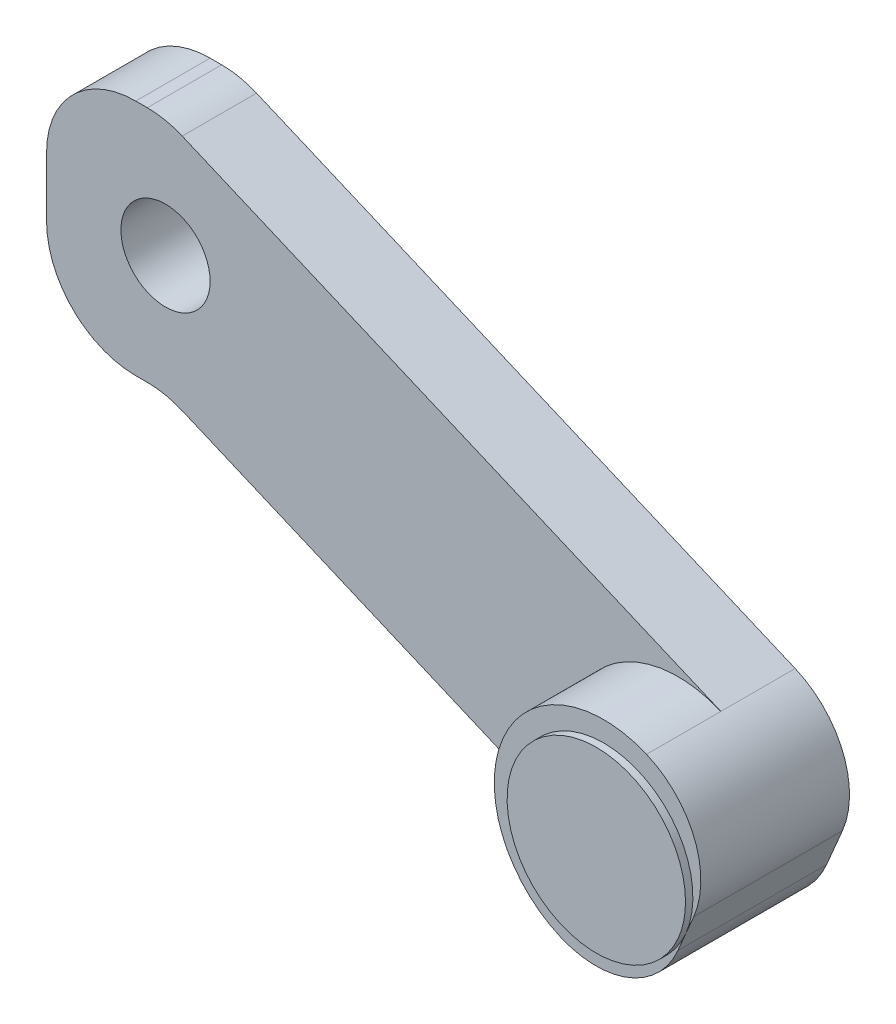
SolidWorks part; units mm, degrees
ref_plane "Plano frontal" through (0, 0, 0) normal (0, 0, 1) x (1, 0, 0)
ref_plane "Plano superior" through (0, 0, 0) normal (0, 1, 0) x (1, 0, 0)
ref_plane "Plano direito" through (0, 0, 0) normal (1, 0, 0) x (0, 0, -1)
sketch "Esboço1" plane through (0, 0, 0) normal (0, 0, 1) x (1, 0, 0)
  line L0 (-8, -8) -> (-8, 8)
  line L5 (-8, 8) -> (0, 8)
  line L6 (0, 8) -> (42.8798, -10.2239)
  line L7 (42.8798, -10.2239) -> (37.1202, -23.7761)
  line L8 (37.1202, -23.7761) -> (0, -8)
  line L9 (0, -8) -> (-8, -8)
  line L10 (-17.8615, 0) -> (30.3176, 0) construction
  circle A0 centre (0, 0) radius 3
  point P0 (0, 0)
  point P14 (40, -17)
  dimension "D3" = 6
  dimension "D1" = 8
  dimension "D2" = 8
  dimension "D4" = 17
  dimension "D5" = 40
extrude "Ressalto-extrusão1" add sketch "Esboço1" along normal blind 5 contours L5 L6 L7 L8 L9 L0 | A0
fillet "Filete1" radius 6 6 edges at (0, -8, 2.5) (-8, -8, 2.5) (-8, 8, 2.5) (0, 8, 2.5) (42.8798, -10.2239, 2.5) (37.1202, -23.7761, 2.5)
sketch "Esboço2" plane through (0, 0, 5) normal (0, 0, 1) x (1, 0, 0)
  line L3 (39.467, -18.2541) -> (40.533, -15.7459)
  line L4 (39.467, -18.2541) -> (40.533, -15.7459)
  arc A4 (37.3578, -7.8771) -> (35.7183, -7.3957) centre (34.478, -14.6532) ccw
  arc A5 (35.7183, -7.3957) -> (31.5982, -21.4292) centre (34.478, -14.6532) ccw
  arc A6 (31.5982, -21.4292) -> (39.467, -18.2541) centre (33.945, -15.9072) ccw
  arc A7 (40.533, -15.7459) -> (37.3578, -7.8771) centre (35.011, -13.3991) ccw
  arc A8 (31.5982, -21.4292) -> (39.467, -18.2541) centre (33.945, -15.9072) ccw
  arc A9 (40.533, -15.7459) -> (37.3578, -7.8771) centre (35.011, -13.3991) ccw
  dimension "D1" = 0
extrude "Ressalto-extrusão2" add sketch "Esboço2" along normal blind 5
sketch "Esboço3" plane through (0, 0, 10) normal (0, 0, 1) x (1, 0, 0)
  circle A0 centre (34.478, -14.6532) radius 6
  arc A1 (37.3578, -7.8771) -> (31.5982, -21.4292) centre (34.478, -14.6532) ccw construction
  point P2 (0, 0)
  dimension "D1" = 12
extrude "Ressalto-extrusão3" add sketch "Esboço3" along normal blind 0.5
